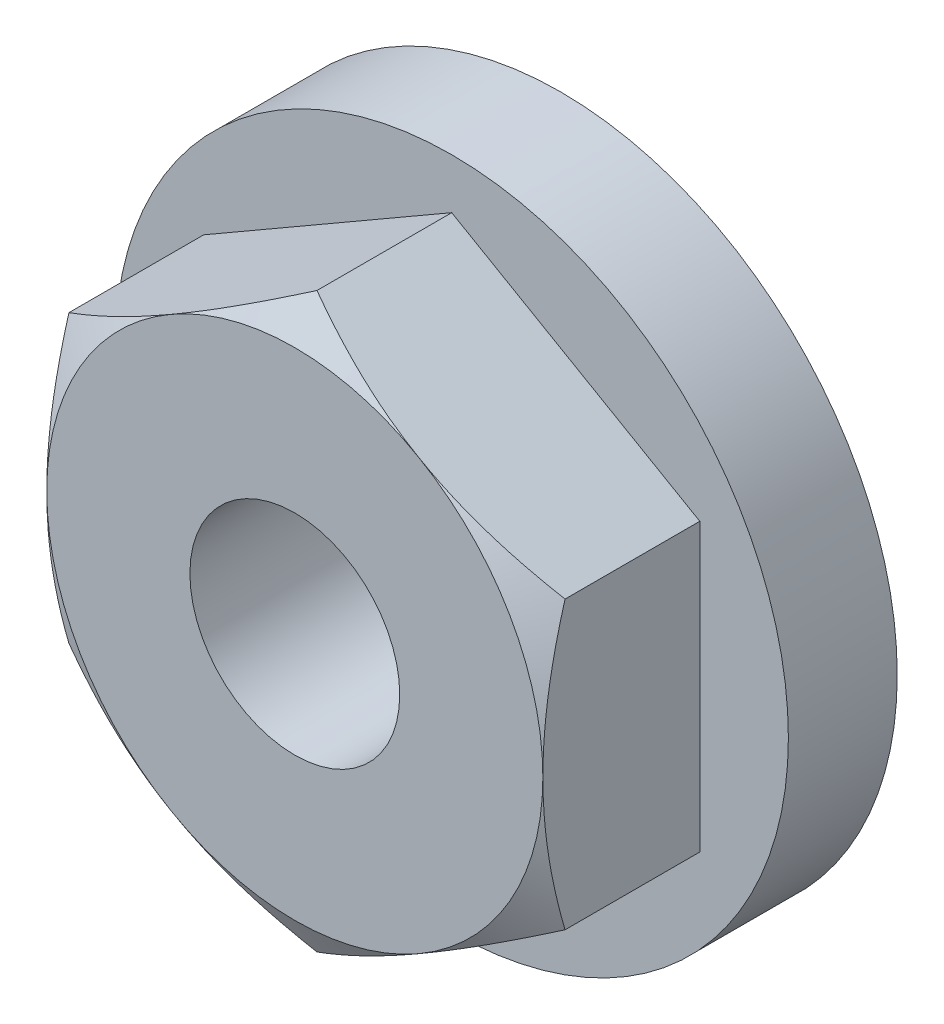
SolidWorks part; units mm, degrees
ref_plane "Front Plane" through (0, 0, 0) normal (0, 0, 1) x (1, 0, 0)
ref_plane "Top Plane" through (0, 0, 0) normal (0, 1, 0) x (1, 0, 0)
ref_plane "Right Plane" through (0, 0, 0) normal (1, 0, 0) x (0, 0, -1)
sketch "Sketch1" plane through (0, 0, 0) normal (0, 0, 1) x (1, 0, 0)
  line L1 (0, 6.4158) -> (-5.5563, 3.2079)
  line L2 (-5.5563, 3.2079) -> (-5.5563, -3.2079)
  line L3 (-5.5563, -3.2079) -> (0, -6.4158)
  line L4 (0, -6.4158) -> (5.5562, -3.2079)
  line L5 (5.5562, -3.2079) -> (5.5562, 3.2079)
  line L6 (5.5562, 3.2079) -> (0, 6.4158)
  circle A0 centre (0, 0) radius 5.5563 construction
  dimension "Hex" = 11.1125
extrude "Extrude1" add sketch "Sketch1" against normal blind 5.9531
sketch "Sketch13" plane through (0, 0, -5.9531) normal (0, 0, -1) x (-1, 0, 0)
  circle A0 centre (0, 0) radius 7.5406
  dimension "Flange od" = 15.0812
extrude "Extrude3" add sketch "Sketch13" against normal blind 2.4384
sketch "Sketch2" plane through (0, 0, 0) normal (0, 0, 1) x (1, 0, 0)
  circle A0 centre (0, 0) radius 5.5563 construction
  circle A1 centre (0, 0) radius 5.5563
extrude "Cut-Extrude1" cut sketch "Sketch2" against normal through all draft 60 flip side to cut
sketch "Sketch4" plane through (0, 0, 0) normal (0, 0, 1) x (1, 0, 0)
  circle A0 centre (0, 0) radius 3.175
  dimension "Thread Dia" = 6.35
extrude "Cut-Extrude3" cut sketch "Sketch4" against normal through all
sketch "Sketch7" plane through (0, 0, 0) normal (0, 0, 1) x (1, 0, 0)
  circle A4 centre (0, 0) radius 3.429
  circle A5 centre (0, 0) radius 3.429
  dimension "D1" = 0.254
sketch "Sketch8" plane through (0, 0, -5.9531) normal (0, 0, -1) x (-1, 0, 0)
  circle A1 centre (0, 0) radius 3.429
  circle A2 centre (0, 0) radius 3.429 construction
sketch "Sketch5" plane through (0, 0, 0) normal (0, 0, 1) x (1, 0, 0)
  circle A0 centre (0, 0) radius 3.175 construction
  circle A1 centre (0, 0) radius 3.175
curve "Helix/Spiral1" pitch 1.27 height 7.2231 turns 5.6875 parameters "pitch"=1.27
sketch "Sketch9" plane through (0, 0, 0) normal (1, 0, 0) x (0, 0, -1)
  line L0 (-0.635, 3.175) -> (-0.4762, 3.175)
  line L1 (-0.4762, 3.175) -> (0, 2.3501)
  line L2 (-0.635, 3.175) -> (-1.1112, 2.3501)
  line L3 (-1.1112, 2.3501) -> (0, 2.3501)
  line L4 (-0.5556, 3.175) -> (-0.5556, 2.3501) construction
  line L5 (-0.8731, 2.7626) -> (-0.2381, 2.7626) construction
  line L7 (0, 2.3501) -> (0, 3.175) construction
  line L8 (0, 3.175) -> (0, -3.175) construction
  dimension "D1" = 0.1588
  dimension "D2" = 0.635
  dimension "D3" = 60
sketch "Sketch12" plane through (0, 0, 0) normal (0, 0, 1) x (1, 0, 0)
  circle A0 centre (0, 0) radius 2.3501
  circle A1 centre (0, 0) radius 3.175 construction
  circle A2 centre (0, 0) radius 3.175
extrude "Extrude2" add sketch "Sketch12" against normal up to surface (5.9531 mm away) up to face at (3.175, 0, -5.9531)
sweep "Cut-Sweep1" [suppressed] cut profiles "Sketch9" path "Helix/Spiral1"
extrude "Cut-Extrude6" [suppressed] cut sketch "Sketch7" against normal through all draft 45
extrude "Cut-Extrude7" [suppressed] cut sketch "Sketch8" against normal through all draft 45
sketch "Sketch14" [suppressed] plane through (0, 0, -5.9531) normal (0, 0, -1) x (-1, 0, 0)
  circle A4 centre (0, 0) radius 5.461
  circle A5 centre (0, 0) radius 5.461
  dimension "D1" = 2.032
extrude "Cut-Extrude8" [suppressed] cut sketch "Sketch14" against normal blind 0.2438 flip side to cut
sketch "Sketch15" [suppressed] plane through (0, 0, -5.7093) normal (0, 0, -1) x (-1, 0, 0)
  line L0 (-0.5353, 5.4347) -> (-0.7391, 7.5043)
  line L1 (0.5353, 5.4347) -> (0.7391, 7.5043)
  line L2 (0, 0) -> (0.5353, 5.4347) construction
  line L3 (0, 0) -> (-0.5353, 5.4347) construction
  circle A0 centre (0, 0) radius 7.5406 construction
  circle A1 centre (0, 0) radius 5.461 construction
  arc A2 (0.7391, 7.5043) -> (-0.7391, 7.5043) centre (0, 0) ccw
  arc A3 (0.5353, 5.4347) -> (-0.5353, 5.4347) centre (0, 0) ccw
  dimension "D1" = 11.25
extrude "Extrude4" [suppressed] add sketch "Sketch15" along normal up to surface (0.2438 mm away) separate body up to face at (-7.5406, 0, -5.9531)
sketch "Sketch16" [suppressed] plane through (0, 0, 0) normal (0, 1, 0) x (1, 0, 0)
  line L0 (-0.7391, 5.7093) -> (0.7391, 5.9531)
  line L4 (-0.7391, 5.7093) -> (0.7391, 5.7093)
  line L5 (0.7391, 5.7093) -> (0.7391, 5.9531)
  line L6 (0.7391, 5.9531) -> (-0.7391, 5.9531)
  line L7 (-0.7391, 5.9531) -> (-0.7391, 5.7093)
  line L8 (-0.7391, 5.7093) -> (0.7391, 5.7093) construction
  line L9 (0.7391, 5.7093) -> (0.7391, 5.9531) construction
  line L10 (0.7391, 5.9531) -> (-0.7391, 5.9531)
  line L11 (-0.7391, 5.9531) -> (-0.7391, 5.7093)
  dimension "D1" = 0
extrude "Cut-Extrude9" [suppressed] cut sketch "Sketch16" along normal through all
pattern_circular "CirPattern1" [suppressed] count 32 over 360 of bodies 119
combine bodies "Combine1" [suppressed] operation type add bodies to combine 117 119 120 121 122 123 124 125 126 127 128 129 130 131 132 133 134 135 136 137 139 140 141 142 143 144 145 146 147 148 149 150 151 152 153 154 155
sketch "Sketch17" [suppressed] plane through (0, 0, 0) normal (1, 0, 0) x (0, 0, -1)
  line L0 (5.9531, 7.5406) -> (5.9531, -7.5406) construction
  line L1 (3.5147, 7.5406) -> (3.5147, -7.5406) construction
  dimension "D1" = 2.4384
sketch "Sketch18" plane through (0, 0, -3.5147) normal (0, 0, 1) x (1, 0, 0)
  circle A0 centre (0, 0) radius 7.5406
  circle A1 centre (0, 0) radius 7.5406 construction
equation "\"D2@Sketch9\" = \"pitch@Helix/Spiral1\"*.5"
equation "\"D3@Helix/Spiral1\" = \"pitch@Helix/Spiral1\"+\"Height@Extrude1\""
equation "\"D1@Sketch9\" = \"pitch@Helix/Spiral1\"*.125"
equation "\"D1@Cut-Extrude8\" = \"flange thickness@Extrude3\"*.1"
equation "\"D1@Sketch17\" = \"flange thickness@Extrude3\""
